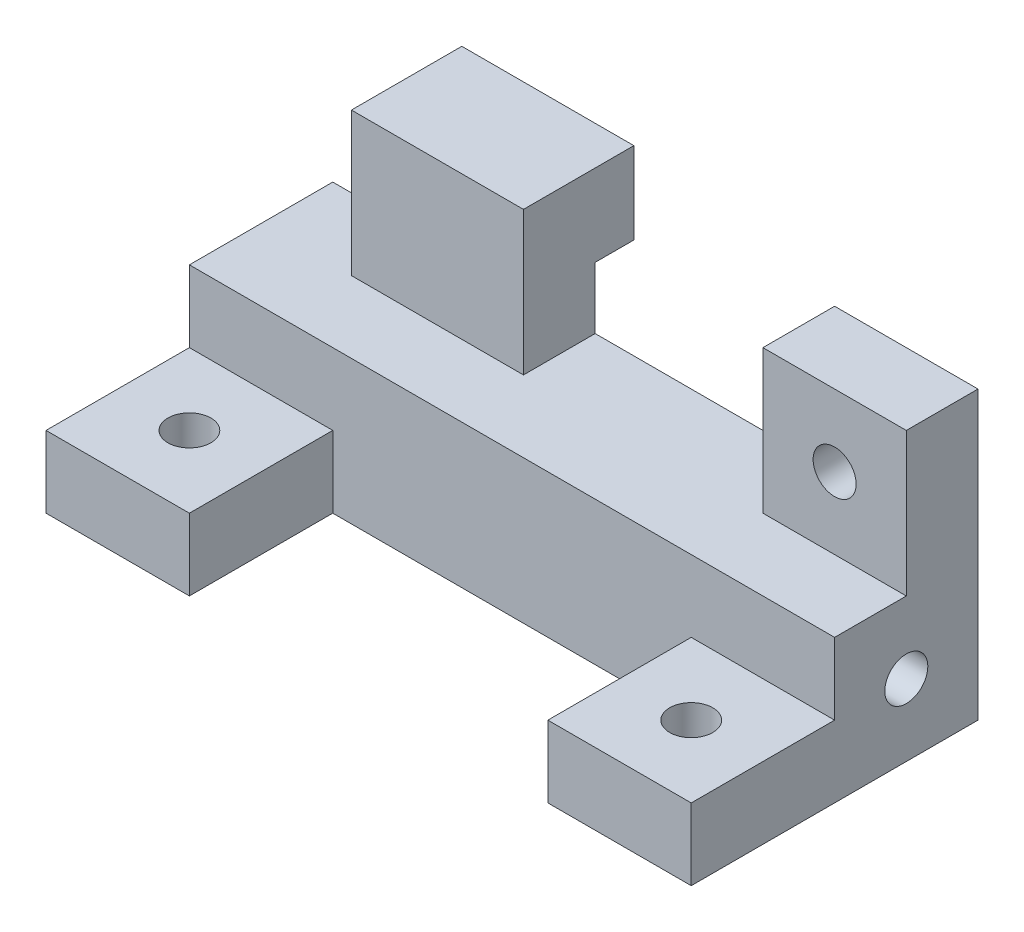
SolidWorks part; units mm, degrees
ref_plane "Front Plane" through (0, 0, 0) normal (0, 0, 1) x (1, 0, 0)
ref_plane "Top Plane" through (0, 0, 0) normal (0, 1, 0) x (1, 0, 0)
ref_plane "Right Plane" through (0, 0, 0) normal (1, 0, 0) x (0, 0, -1)
sketch "Sketch1" plane through (0, 0, 0) normal (0, 0, 1) x (1, 0, 0)
  line L1 (0, 0) -> (45, 0)
  line L2 (0, 0) -> (0, 10)
  line L3 (0, 10) -> (45, 10)
  line L4 (45, 0) -> (45, 10)
  dimension "D1" = 45
  dimension "D2" = 10
extrude "Boss-Extrude1" add sketch "Sketch1" along normal blind 10
sketch "Sketch2" plane through (0, 10, 0) normal (0, 1, 0) x (1, 0, 0)
  line L0 (45, 0) -> (0, 0) construction
  line L1 (45, 0) -> (35, 0)
  line L2 (45, 0) -> (45, -5)
  line L3 (45, -5) -> (35, -5)
  line L4 (35, 0) -> (35, -5)
  line L5 (6.3, 0) -> (18.3, 0)
  line L6 (6.3, 0) -> (6.3, -5)
  line L7 (6.3, -5) -> (18.3, -5)
  line L8 (18.3, 0) -> (18.3, -5)
  line L9 (0, -10) -> (0, 0) construction
  dimension "D1" = 5
  dimension "D2" = 10
  dimension "D3" = 5
  dimension "D4" = 6.3
  dimension "D5" = 12
extrude "Boss-Extrude2" add sketch "Sketch2" along normal blind 10
sketch "Sketch3" plane through (0, 0, 10) normal (0, 0, 1) x (1, 0, 0)
  line L1 (0, 0) -> (10, 0)
  line L2 (0, 0) -> (0, 5)
  line L3 (0, 5) -> (10, 5)
  line L4 (10, 0) -> (10, 5)
  line L5 (45, 0) -> (35, 0)
  line L6 (45, 0) -> (45, 5)
  line L7 (45, 5) -> (35, 5)
  line L8 (35, 0) -> (35, 5)
  dimension "D1" = 10
  dimension "D2" = 10
  dimension "D3" = 5
  dimension "D4" = 5
extrude "Boss-Extrude3" add sketch "Sketch3" along normal blind 10
sketch "Sketch4" plane through (0, 0, 0) normal (-1, 0, 0) x (0, 0, 1)
  line L0 (0, 10) -> (0, 0) construction
  line L1 (20, 0) -> (0, 0) construction
  circle A0 centre (5, 5) radius 1.5
  dimension "D3" = 3
  dimension "D1" = 5
  dimension "D2" = 5
extrude "Cut-Extrude1" cut sketch "Sketch4" against normal blind 5
sketch "Sketch6" plane through (0, 5, 0) normal (0, 1, 0) x (1, 0, 0)
  line L0 (10, -20) -> (10, -10) construction
  line L1 (10, -20) -> (0, -20) construction
  circle A0 centre (5, -15) radius 1.5
  dimension "D3" = 3
  dimension "D1" = 5
  dimension "D2" = 5
extrude "Cut-Extrude3" cut sketch "Sketch6" against normal blind 5
sketch "Sketch7" plane through (45, 0, 0) normal (1, 0, 0) x (0, 0, -1)
  line L0 (0, 0) -> (0, 20) construction
  line L1 (-10, 10) -> (-5, 10) construction
  circle A0 centre (-5, 5) radius 1.5
  dimension "D3" = 3
  dimension "D1" = 5
  dimension "D2" = 5
extrude "Cut-Extrude4" cut sketch "Sketch7" against normal blind 5
sketch "Sketch9" plane through (0, 5, 0) normal (0, 1, 0) x (1, 0, 0)
  line L0 (45, -20) -> (45, -10) construction
  line L1 (45, -20) -> (35, -20) construction
  circle A0 centre (40, -15) radius 1.5
  dimension "D3" = 3
  dimension "D1" = 5
  dimension "D2" = 5
extrude "Cut-Extrude6" cut sketch "Sketch9" against normal blind 5
sketch "Sketch10" plane through (0, 0, 5) normal (0, 0, 1) x (1, 0, 0)
  line L0 (35, 20) -> (35, 10) construction
  line L3 (35, 10) -> (45, 10) construction
  circle A0 centre (40, 15) radius 1.5
  dimension "D3" = 3
  dimension "D1" = 5
  dimension "D2" = 5
extrude "Cut-Extrude7" cut sketch "Sketch10" against normal blind 5
sketch "Sketch11" plane through (0, 0, 0) normal (0, 0, -1) x (-1, 0, 0)
  line L0 (-18.3, 20) -> (-18.3, 10) construction
  line L1 (-6.3, 20) -> (-18.3, 20)
  line L2 (-6.3, 20) -> (-6.3, 14.3)
  line L3 (-6.3, 14.3) -> (-18.3, 14.3)
  line L4 (-18.3, 20) -> (-18.3, 14.3)
  line L5 (-18.3, 14.3) -> (-6.3, 14.3) construction
extrude "Boss-Extrude4" add sketch "Sketch11" along normal blind 2.7
